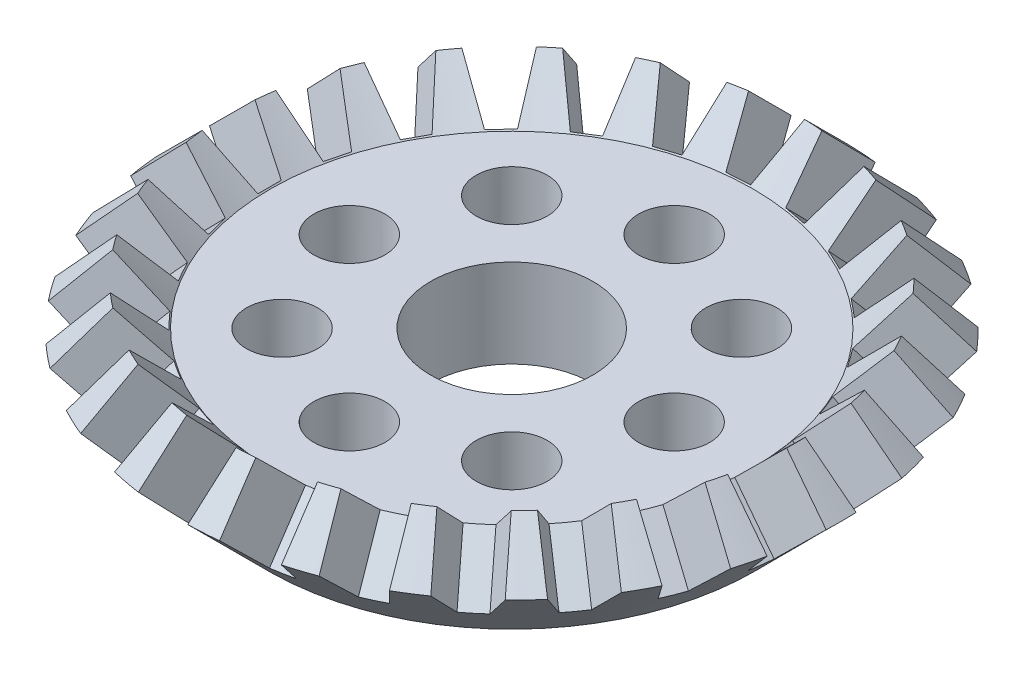
SolidWorks part; units mm, degrees
ref_plane "Front Plane" through (0, 0, 0) normal (0, 0, 1) x (1, 0, 0)
ref_plane "Top Plane" through (0, 0, 0) normal (0, 1, 0) x (1, 0, 0)
ref_plane "Right Plane" through (0, 0, 0) normal (1, 0, 0) x (0, 0, -1)
sketch "Sketch2" plane through (0, 0, 0) normal (0, 0, 1) x (1, 0, 0)
  line L6 (0, 0) -> (0, 4.3558)
  line L7 (0, 0) -> (-12, 0)
  line L9 (-12, 0) -> (-16.2426, 4.2426)
  line L14 (-16.2426, 4.2426) -> (-14.0081, 6.4771)
  line L15 (-11.8868, 4.3558) -> (-14.0081, 6.4771)
  line L16 (-11.8868, 4.3558) -> (0, 4.3558)
  dimension "D2" = 12
  dimension "D4" = 45
  dimension "D5" = 6
  dimension "D6" = 3
revolve "Revolve4" add sketch "Sketch2" angle 360 about L6
sketch "Sketch3" plane through (0, 0, 0) normal (0, 0, 1) x (1, 0, 0)
  line L0 (0, 0) -> (0, 20.4853) construction
  line L1 (0, 20.4853) -> (0, -16.6359) construction
  line L2 (0, 20.4853) -> (-22.6315, -2.1462) construction
  line L3 (-14.0081, 6.4771) -> (-16.2426, 4.2426) construction
ref_plane "Plane1" through (-6, -6, 0) normal (-0.7071, -0.7071, 0) x (0, 0, 1)
sketch "Sketch4" plane through (-6, -6, 0) normal (-0.7071, -0.7071, 0) x (0, 0, 1)
  line L0 (0, 9.4379) -> (0, 20.3385) construction
  line L1 (0, 0) -> (0, 14.4853) construction
  line L8 (-0.5759, 11.5564) -> (0.5759, 11.5564)
  line L9 (0.5759, 11.5564) -> (1.4119, 14.8882)
  line L10 (1.4119, 14.8882) -> (-1.4119, 14.8882)
  line L11 (-0.5759, 11.5564) -> (-1.4119, 14.8882)
  point P9 (0, 12.845)
  point P10 (0, 11.5564)
  point P11 (0, 14.0042)
  point P12 (0, 14.8882)
  point P13 (0, 17.9558)
  point P14 (0, 14.0042)
  point P15 (0, 17.9558)
  point P16 (0, 0)
  point P17 (0.7471, 12.7911)
  point P18 (0, 0)
  point P19 (1.4119, 14.8882)
  point P20 (0, 11.7237)
  point P21 (-0.6179, 11.7237)
  point P22 (0, 0)
  point P23 (0, 0)
  point P24 (0, 12.7952)
  point P25 (0, 11.8582)
  point P26 (0, 12.6973)
  point P27 (0, 0)
  point P28 (0, 12.1956)
  point P29 (0, 11.9507)
  point P30 (0, 11.6989)
  point P31 (0, 11.5564)
extrude "Cut-Extrude11" cut sketch "Sketch4" against normal blind 10 contours L10 L11 L8 L9
sketch "Sketch5" plane through (0, 4.3558, 0) normal (0, 1, 0) x (1, 0, 0)
  line L0 (0, 0) -> (0, -8)
  circle A0 centre (0, 0) radius 4
  circle A1 centre (0, -8) radius 1.75
  dimension "D1" = 8
  dimension "D3" = 3.5
  dimension "D2" = 8
extrude "Cut-Extrude12" cut sketch "Sketch5" against normal blind 10 contours A0 region at (-2.7484, 4.3558, -2.7484)
extrude "Cut-Extrude13" cut sketch "Sketch5<3>" against normal blind 10 contours A1
sketch "Sketch5<3>" plane through (0, 4.3558, 0) normal (0, 1, 0) x (1, 0, 0) same geometry as "Sketch5"
pattern_circular "CirPattern13" count 8 over 360 about axis through (0, 20.4853, 0) along (0, -1, 0) of "Cut-Extrude13"
pattern_circular "CirPattern14" count 25 over 360 about axis through (0, 0, 0) along (0, 1, 0) of "Cut-Extrude11" reverse direction yes
